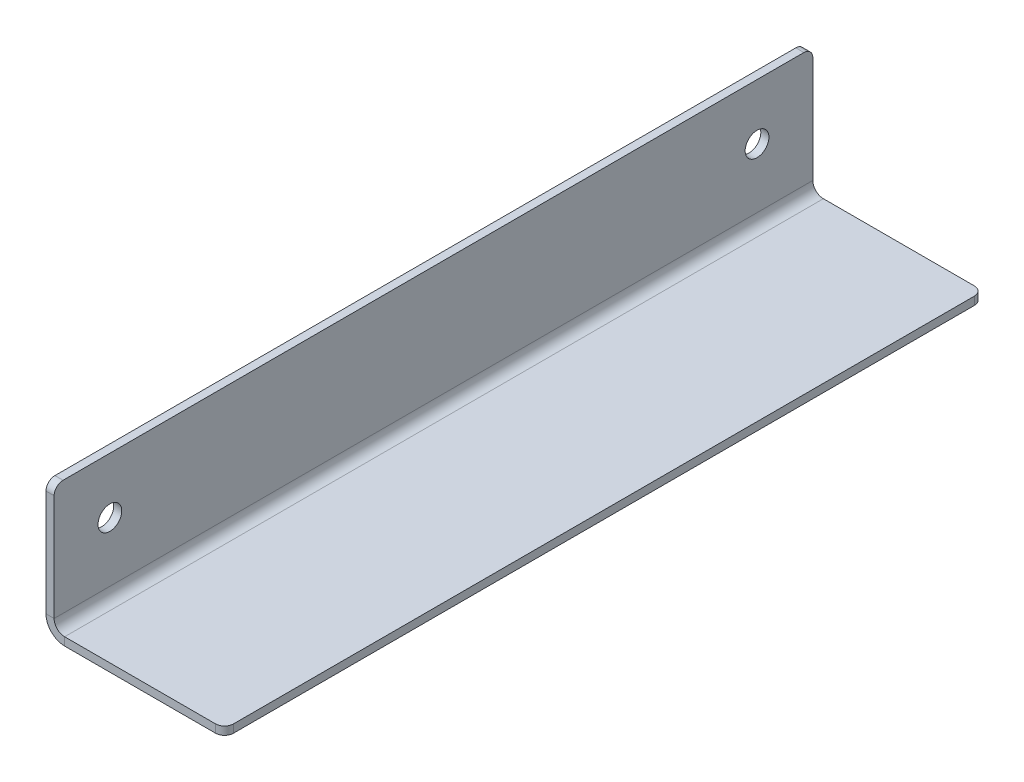
SolidWorks part; units mm, degrees
note: The reader was unsure of these and kept them because the rebuilt part matched: thickness of "Base-Flange1", "Edge-Flange1", "Sheet-Metal1", "Sheet-Metal2", "Sheet-Metal3"; flange length of "Edge-Flange1".
material "6061 Alloy"
ref_plane "Front Plane" through (0, 0, 0) normal (0, 0, 1) x (1, 0, 0)
ref_plane "Top Plane" through (0, 0, 0) normal (0, 1, 0) x (1, 0, 0)
ref_plane "Right Plane" through (0, 0, 0) normal (1, 0, 0) x (0, 0, -1)
sketch "Sketch1" plane through (0, 0, 0) normal (1, 0, 0) x (0, -1, 0)
  line L1 (0, 0) -> (-38.1, 0)
  line L2 (0, 0) -> (0, -215.9)
  line L3 (0, -215.9) -> (-38.1, -215.9)
  line L4 (-38.1, 0) -> (-38.1, -215.9)
  dimension "D1" = 38.1
  dimension "D2" = 215.9
base flange "Base-Flange1" sketch "Sketch1" thickness 2.3048 reverse thickness direction no parameters "D1"=3
edge flange "Edge-Flange1" sketch "Sketch8" flange angle 90 flange length 50.8 flange position material inside bend radius 3 thickness 2.3048 relief rectangular parameters "D6"=10
sketch "Sketch8" plane through (0, 0, 0) normal (0, -1, 0) x (0, 0, -1)
  line L0 (-215.9, 0) -> (0, 0) construction
  line L1 (-215.9, 0) -> (0, 0)
  line L2 (-215.9, 0) -> (-215.9, 48.4952)
  line L3 (-215.9, 48.4952) -> (0, 48.4952)
  line L4 (0, 48.4952) -> (0, 0)
bend "EdgeBend1" bend radius 3 bend angle 90 parameters "D5"=1
hole_wizard "1/4 Clearance Hole1" positions "Sketch9" profile "Sketch10" hole size "1/4" standard "ANSI Inch" end condition through all
sketch "Sketch9" plane through (-2.3048, 0, 0) normal (-1, 0, 0) x (0, 0, 1)
  line L0 (107.95, 38.1) -> (107.95, 0) construction
  line L1 (0, 38.1) -> (215.9, 38.1) construction
  line L2 (0, 0) -> (215.9, 0) construction
  point P0 (15.875, 22.225)
  point P2 (200.025, 22.225)
  dimension "D1" = 15.875
  dimension "D2" = 184.15
sketch "Sketch10" plane through (-2.3048, 22.225, 15.875) normal (0, 1, 0) x (0, 0, 1)
  line L0 (0, 0) -> (0, 50.8)
  line L1 (0, 50.8) -> (3.3782, 50.8)
  line L2 (3.3782, 50.8) -> (3.3782, 0)
  line L5 (3.3782, 0) -> (0, 0)
  line L11 (0, -6.35) -> (0, 107.95) construction
  dimension "Thru Hole Dia." = 6.7564
  dimension "Thru Hole Depth" = 50.8
fillet "Fillet1" radius 2.54 4 edges at (-1.1524, 38.1, 0) (48.4952, 1.1524, 0) (48.4952, 1.1524, 215.9) (-1.1524, 38.1, 215.9)
sketch "Bend-Lines1" [suppressed] plane through (0, 0, 0) normal (0, 1, 0) x (1, 0, 0)
sketch "Bounding-Box1" [suppressed] plane through (0, 0, 0) normal (0, 1, 0) x (1, 0, 0)
sheet metal parameters "Sheet-Metal1" thickness 2.3048 parameters "D1"=3, "D7"=2.3622
flat pattern "Flat-Pattern1" [suppressed]
sketch "Bend-Lines2" plane through (0, 0, 0) normal (0, 1, 0) x (1, 0, 0)
sketch3d "Bounding-Box2" [suppressed]
  line L0 (0, 0, 0) -> (-127, 0, 0) construction
  line L1 (0, 38.1, 0) -> (-127, 38.1, 0) construction
  line L2 (0, 0, 0) -> (0, 38.1, 0) construction
  line L3 (-127, 0, 0) -> (-127, 38.1, 0) construction
sheet metal parameters "Sheet-Metal2" thickness 2.3048 parameters "D1"=3, "D7"=2.3622
flat pattern "Flat-Pattern1"
sketch "Bend-Lines2" plane through (0, 0, 0) normal (1, 0, 0) x (0, 0, -1)
  line L0 (-127, 2.0784) -> (0, 2.0784) construction
  line L1 (-127, 2.0784) -> (0, 2.0784) construction
sketch3d "Bounding-Box2" [suppressed]
  line L0 (0, -46.6433, 0) -> (-127, -46.6433, 0) construction
  line L1 (0, 38.1, 0) -> (-127, 38.1, 0) construction
  line L2 (0, -46.6433, 0) -> (0, 38.1, 0) construction
  line L3 (-127, -46.6433, 0) -> (-127, 38.1, 0) construction
bend of the flat pattern "Flatten-<EdgeBend1>1"
sheet metal parameters "Sheet-Metal3" thickness 2.3048 parameters "D1"=3, "D7"=2.3622
flat pattern "Flat-Pattern1"
sketch "Bend-Lines2" plane through (0, 0, 0) normal (1, 0, 0) x (0, 0, -1)
  line L0 (-215.9, 2.0435) -> (0, 2.0435) construction
  line L1 (-215.9, 2.0435) -> (0, 2.0435) construction
sketch3d "Bounding-Box2" [suppressed]
  line L0 (0, -46.713, 0) -> (-215.9, -46.713, 0) construction
  line L1 (0, 38.1, 0) -> (-215.9, 38.1, 0) construction
  line L2 (0, -46.713, 0) -> (0, 38.1, 0) construction
  line L3 (-215.9, -46.713, 0) -> (-215.9, 38.1, 0) construction
bend of the flat pattern "Flatten-<EdgeBend1>1"
